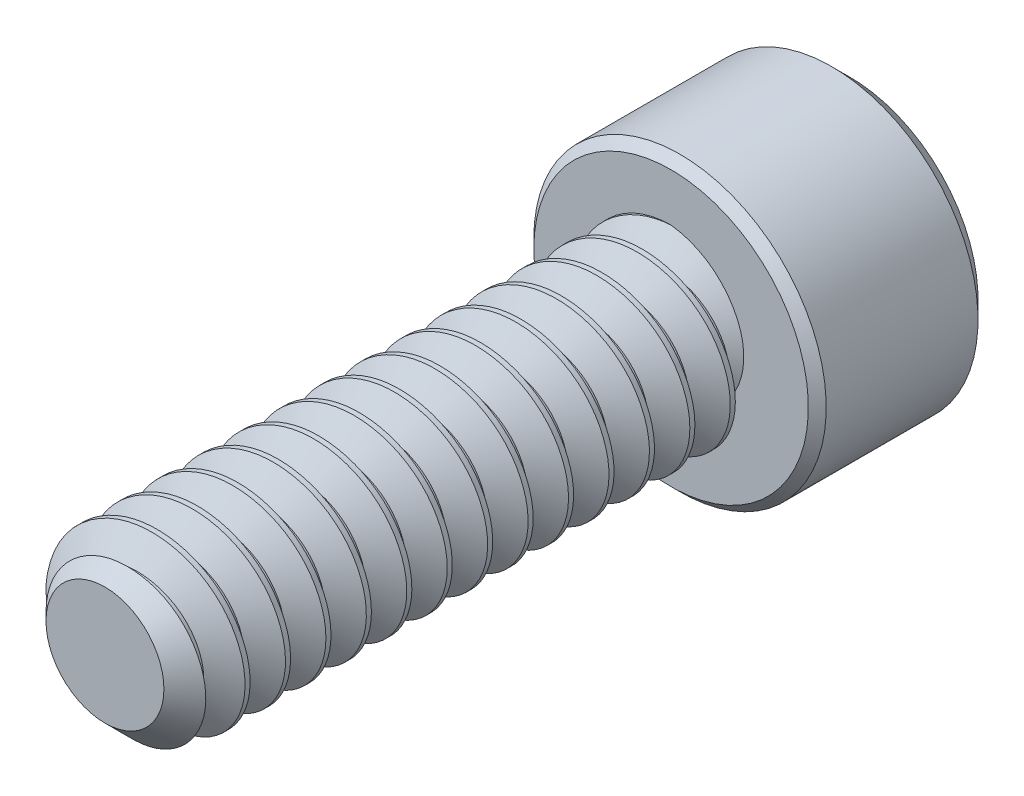
SolidWorks part; units mm, degrees
ref_plane "Front Plane" through (0, 0, 0) normal (0, 0, 1) x (1, 0, 0)
ref_plane "Top Plane" through (0, 0, 0) normal (0, 1, 0) x (1, 0, 0)
ref_plane "Right Plane" through (0, 0, 0) normal (1, 0, 0) x (0, 0, -1)
sketch "Sketch1" plane through (0, 0, 0) normal (0, 0, 1) x (1, 0, 0)
  line L0 (0, 1.7526) -> (0, -1.7526) construction
  circle A0 centre (0, 0) radius 1.7526
  dimension "OD" = 3.5052
extrude "Extrude1" add sketch "Sketch1" against normal blind 11.1125
sketch "Sketch2" plane through (0, 0, 0) normal (0, 0, 1) x (1, 0, 0)
  circle A0 centre (0, 0) radius 1.7526 construction
  circle A1 centre (0, 0) radius 1.7526
curve "Helix/Spiral1" pitch 0.7937 height 11.9062 turns 15 parameters "pitch"=0.7937
chamfer "Chamfer3" distance 0.5953 angle 45 1 edges at (1.7526, 0, 0)
sketch "Sketch3" plane through (0, 0, 0) normal (1, 0, 0) x (0, 0, -1)
  line L0 (-0.6945, 1.7526) -> (-0.3969, 1.237)
  line L1 (-0.3969, 1.237) -> (-0.2977, 1.237)
  line L2 (-0.2977, 1.237) -> (0, 1.7526)
  line L3 (-0.6945, 1.7526) -> (0, 1.7526)
  line L4 (-0.3473, 1.7526) -> (-0.3473, 1.237) construction
  line L5 (-0.5457, 1.4948) -> (-0.1488, 1.4948) construction
  line L6 (0, 1.7526) -> (0, -1.7526) construction
  dimension "D1" = 0.0992
  dimension "D2" = 0.3969
  dimension "D3" = 60
sweep "Cut-Sweep1" cut profiles "Sketch3" path "Helix/Spiral1"
sketch "Sketch6" plane through (0, 0, -11.1125) normal (0, 0, -1) x (-1, 0, 0)
  circle A0 centre (0, 0) radius 2.8702
  dimension "head dia" = 5.7404
extrude "Extrude2" add sketch "Sketch6" along normal blind 3.5052
sketch "Sketch7" plane through (0, 0, -14.6177) normal (0, 0, -1) x (-1, 0, 0)
  line L1 (0, 1.604) -> (-1.3891, 0.802)
  line L2 (-1.3891, 0.802) -> (-1.3891, -0.802)
  line L3 (-1.3891, -0.802) -> (0, -1.604)
  line L4 (0, -1.604) -> (1.3891, -0.802)
  line L5 (1.3891, -0.802) -> (1.3891, 0.802)
  line L6 (1.3891, 0.802) -> (0, 1.604)
  circle A0 centre (0, 0) radius 1.3891 construction
  dimension "hex dia" = 2.7781
extrude "Cut-Extrude1" cut sketch "Sketch7" against normal blind 2.0836
sketch "Sketch8" plane through (0, 0, -14.6177) normal (0, 0, -1) x (-1, 0, 0)
  circle A0 centre (0, 0) radius 1.604
extrude "Cut-Extrude2" cut sketch "Sketch8" against normal blind 0.3505 draft 45
chamfer "Chamfer1" distance 0.3505 angle 45 1 edges at (-2.8702, 0, -14.6177)
chamfer "Chamfer2" distance 0.1753 angle 45 1 edges at (-2.8702, 0, -11.1125)
sketch "Sketch9" plane through (0, 0, 0) normal (1, 0, 0) x (0, 0, -1)
  line L0 (0, 1.7526) -> (0, -1.7526) construction
  line L1 (4.3656, 1.7526) -> (4.3656, -1.7526) construction
  line L2 (11.1125, 2.8702) -> (11.1125, -2.8702) construction
  line L3 (14.6177, 2.8702) -> (14.6177, -2.8702) construction
  line L4 (14.6177, 0) -> (0, 0) construction
  dimension "D1" = 4.3656
  dimension "D2" = 3.5052
  dimension "D3" = 5.7404
  dimension "D4" = 11.1125
equation "\"D3@Helix/Spiral1\" = \"screw length@Extrude1\"+\"pitch@Helix/Spiral1\""
equation "\"D1@Sketch3\" = \"pitch@Helix/Spiral1\"*.125"
equation "\"D2@Sketch3\" = \"pitch@Helix/Spiral1\"*.5"
equation "\"D1@Cut-Extrude1\" = \"hex dia@Sketch7\"*.75"
equation "\"D1@Chamfer1\" = \"head depth@Extrude2\"/10"
equation "\"D1@Sketch9\" = \"pitch@Helix/Spiral1\"*5.5"
equation "\"D1@Chamfer2\" = \"D1@Chamfer1\"/2"
equation "\"D1@Cut-Extrude2\" = \"D1@Chamfer2\"*2"
equation "\"D1@Chamfer3\" = \"pitch@Helix/Spiral1\"*.750"
equation "\"D2@Sketch9\" = \"head depth@Extrude2\""
equation "\"D3@Sketch9\" = \"head dia@Sketch6\""
equation "\"D4@Sketch9\" = \"screw length@Extrude1\""
